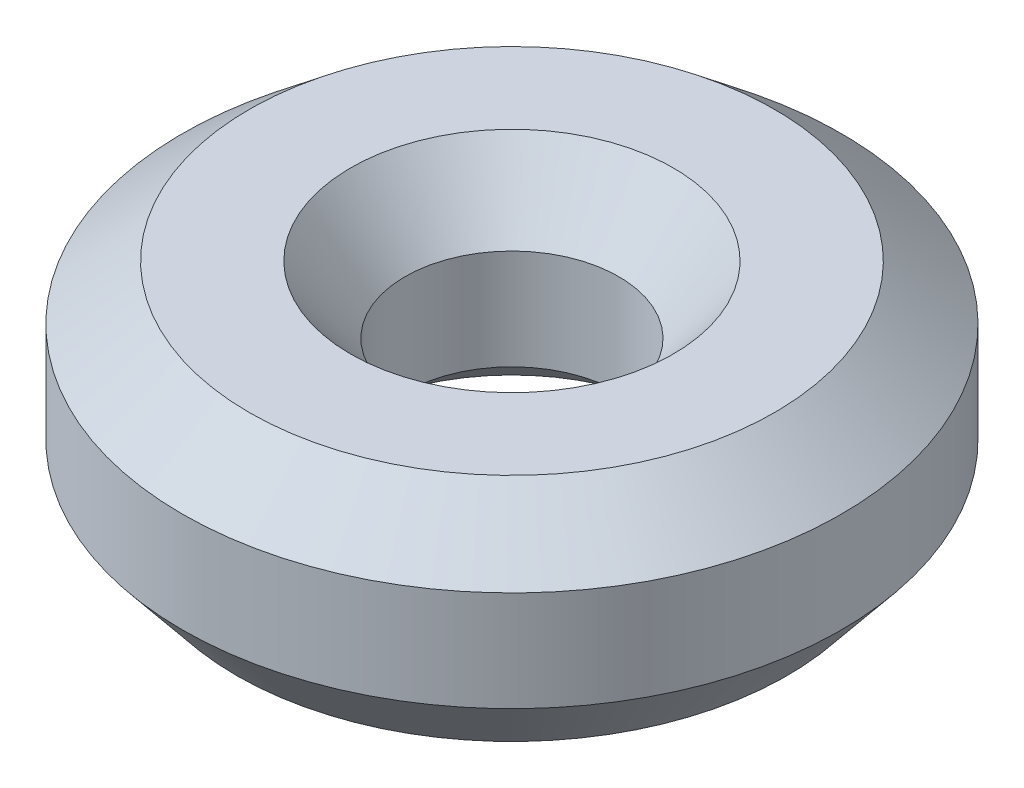
SolidWorks part; units mm, degrees
ref_plane "Front Plane" through (0, 0, 0) normal (0, 0, 1) x (1, 0, 0)
ref_plane "Top Plane" through (0, 0, 0) normal (0, 1, 0) x (1, 0, 0)
ref_plane "Right Plane" through (0, 0, 0) normal (1, 0, 0) x (0, 0, -1)
sketch "Sketch1" plane through (0, 0, 0) normal (0, 1, 0) x (1, 0, 0)
  circle A0 centre (0, 0) radius 10
  dimension "SLEEVE_OD" = 20
extrude "Boss-Extrude1" add sketch "Sketch1" along normal blind 6.7262
sketch "Sketch2" plane through (0, 0, 0) normal (0, 1, 0) x (1, 0, 0)
  circle A0 centre (0, 0) radius 3.2424
  dimension "BORE_D" = 6.4849
extrude "Cut-Extrude1" cut sketch "Sketch2" along normal through all
chamfer "Chamfer1" distance 1.6526 angle 50.873 4 edges at (0, 6.7262, 3.2424) (0, 0, 3.2424) (0, 0, 10) (0, 6.7262, 10) first distance on face at (0, 6.7262, 3.2424) first distance on face at (0, 0, 3.2424) first distance on face at (0, 6.7262, 10)
